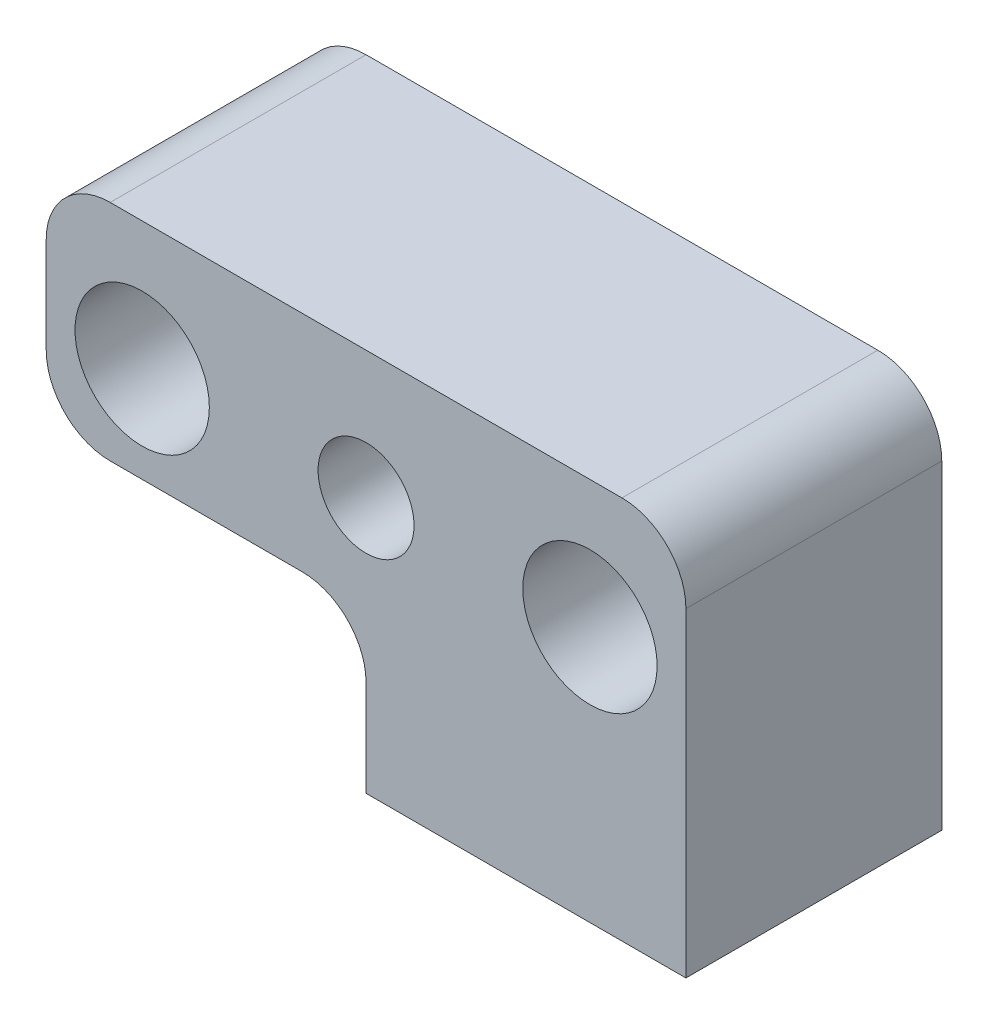
SolidWorks part; units mm, degrees
ref_plane "Front Plane" through (0, 0, 0) normal (0, 0, 1) x (1, 0, 0)
ref_plane "Top Plane" through (0, 0, 0) normal (0, 1, 0) x (1, 0, 0)
ref_plane "Right Plane" through (0, 0, 0) normal (1, 0, 0) x (0, 0, -1)
sketch "Sketch1" plane through (0, 0, 0) normal (0, 0, 1) x (1, 0, 0)
  line L1 (50, -40) -> (-50, -40)
  line L2 (50, -40) -> (50, 40)
  line L3 (50, 40) -> (-50, 40)
  line L4 (-50, -40) -> (-50, 40)
  line L5 (50, -40) -> (-50, 40) construction
  line L6 (50, 40) -> (-50, -40) construction
  point P0 (0, 0)
  dimension "D1" = 100
  dimension "D2" = 80
extrude "Boss-Extrude1" add sketch "Sketch1" along normal blind 40
sketch "Sketch2" plane through (0, 0, 40) normal (0, 0, 1) x (1, 0, 0)
  line L0 (-50, 0) -> (0, 0) construction
  line L1 (-50, 40) -> (-50, -40) construction
  line L2 (0, 0) -> (0, 40) construction
  line L3 (50, 40) -> (-50, 40) construction
  circle A0 centre (0, 0) radius 7.5
  circle A1 centre (-35, 0) radius 10.5
  circle A2 centre (35, 0) radius 10.5
  dimension "D1" = 21
  dimension "D3" = 15
  dimension "D2" = 15
extrude "Cut-Extrude1" cut sketch "Sketch2" against normal up to next
sketch "Sketch3" plane through (0, 0, 40) normal (0, 0, 1) x (1, 0, 0)
  line L0 (50, -40) -> (50, 40) construction
  line L1 (-50, 40) -> (50, 40)
  line L2 (-50, 40) -> (-50, 20)
  line L3 (-50, 20) -> (50, 20)
  line L4 (50, 40) -> (50, 20)
  dimension "D1" = 20
extrude "Cut-Extrude2" cut sketch "Sketch3" against normal up to next
sketch "Sketch4" plane through (0, -40, 0) normal (0, -1, 0) x (1, 0, 0)
  line L0 (-50, 20) -> (-38.6852, 20) construction
  line L1 (-50, 40) -> (-50, 0) construction
  line L2 (50, 40) -> (50, 0) construction
  line L3 (0, 0) -> (0, 40) construction
  line L4 (-50, 40) -> (50, 40) construction
  line L5 (-33.3148, 20) -> (-18.6852, 20) construction
  line L6 (-13.3148, 20) -> (50, 20) construction
  circle A2 centre (16, 20) radius 3
  circle A3 centre (36, 20) radius 3
  dimension "D3" = 6
  dimension "D4" = 6
  dimension "D1" = 34
  dimension "D2" = 14
extrude "Cut-Extrude3" cut sketch "Sketch4" against normal blind 25
sketch "Sketch5" plane through (0, 0, 0) normal (0, 0, -1) x (-1, 0, 0)
  line L1 (50, -40) -> (0, -40)
  line L2 (50, -40) -> (50, -15)
  line L3 (50, -15) -> (0, -15)
  line L4 (0, -40) -> (0, -15)
  dimension "D1" = 50
  dimension "D2" = 25
extrude "Cut-Extrude4" cut sketch "Sketch5" against normal up to next
fillet "Fillet1" radius 10 1 edges at (0, -15, 20) type face fillet first side face at (-25, -15, 20) second side face at (0, -27.5, 20)
fillet "Fillet2" radius 10 1 edges at (-50, -15, 20) type face fillet first side face at (-30, -15, 20) second side face at (-50, 2.5, 20)
fillet "Fillet3" radius 10 1 edges at (-50, 20, 20) type face fillet first side face at (-50, 7.5, 20) second side face at (0, 20, 20)
fillet "Fillet4" radius 10 1 edges at (50, 20, 20) type face fillet first side face at (5, 20, 20) second side face at (50, -10, 20)
